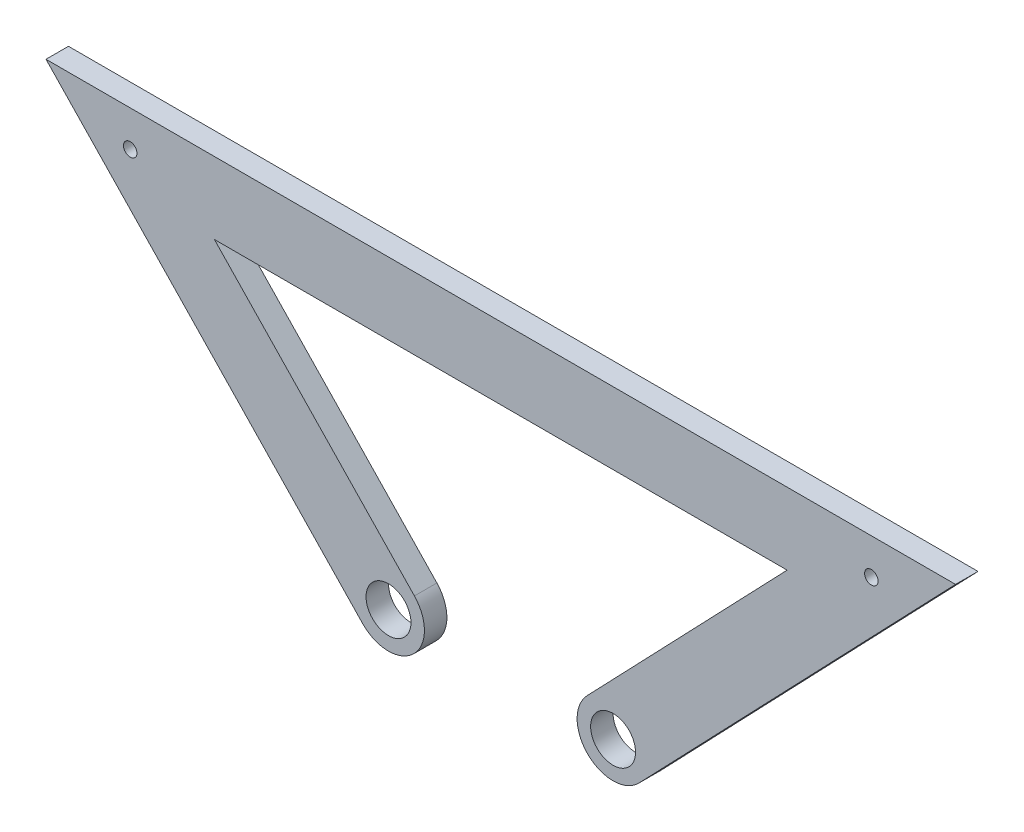
SolidWorks part; units mm, degrees
ref_plane "Front Plane" through (0, 0, 0) normal (0, 0, 1) x (1, 0, 0)
ref_plane "Top Plane" through (0, 0, 0) normal (0, 1, 0) x (1, 0, 0)
ref_plane "Right Plane" through (0, 0, 0) normal (1, 0, 0) x (0, 0, -1)
sketch "Sketch2" plane through (0, 0, 0) normal (0, 0, 1) x (1, 0, 0)
  line L0 (0, 0) -> (0, 120) construction
  line L1 (-165, 120) -> (165, 120) construction
  line L2 (-165, 120) -> (-50, 0) construction
  line L3 (165, 120) -> (50, 0) construction
  line L4 (-127.5056, 104) -> (-38.4482, 11.0705)
  line L5 (-127.5056, 104) -> (127.5056, 104)
  line L6 (127.5056, 104) -> (38.4482, 11.0705)
  line L7 (-202.4944, 136) -> (-61.5518, -11.0705)
  line L8 (-202.4944, 136) -> (202.4944, 136)
  line L9 (202.4944, 136) -> (61.5518, -11.0705)
  arc A0 (-38.4482, 11.0705) -> (-61.5518, -11.0705) centre (-50, 0) cw
  arc A1 (38.4482, 11.0705) -> (61.5518, -11.0705) centre (50, 0) ccw
  circle A2 centre (-165, 120) radius 3
  circle A3 centre (165, 120) radius 3
  circle A4 centre (-50, 0) radius 10
  circle A5 centre (50, 0) radius 10
  circle A6 centre (-48.0974, 9.9508) radius 0.131
  point P5 (0, 120)
  point P8 (165, 120)
  point P11 (-165, 120)
  dimension "D6" = 6
  dimension "D7" = 20
  dimension "D8" = 20
  dimension "D1" = 120
  dimension "D2" = 16
  dimension "D3" = 165
  dimension "D4" = 16
  dimension "D5" = 50
extrude "Boss-Extrude9" add sketch "Sketch2" against normal blind 10 contours L8 L9 A1 L6 L5 L4 A0 L7
extrude "Cut-Extrude1" cut sketch "Sketch2<6>" against normal blind 10 from offset 0 contours A2 | A3 | A5 | A4
sketch "Sketch2<6>" plane through (0, 0, 0) normal (0, 0, 1) x (1, 0, 0) same geometry as "Sketch2"
scale "Scale1" scale about centroid uniform scaling yes scale factor 0.5
